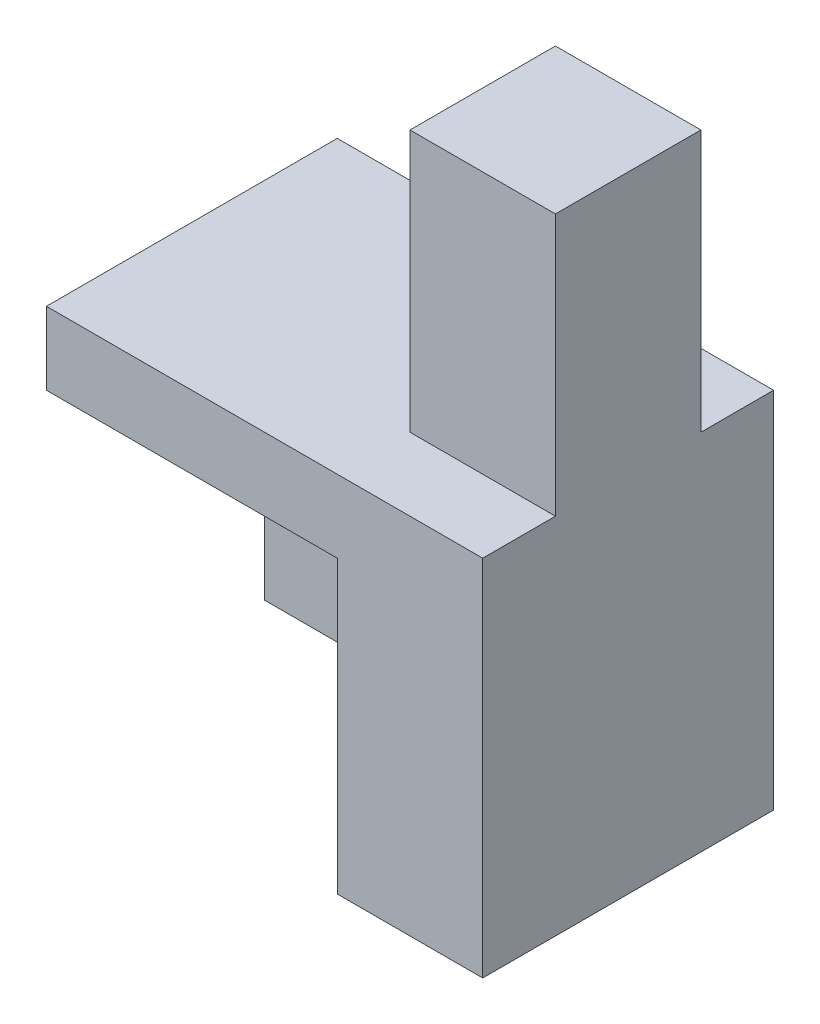
SolidWorks part; units mm, degrees
ref_plane "Front Plane" through (0, 0, 0) normal (0, 0, 1) x (1, 0, 0)
ref_plane "Top Plane" through (0, 0, 0) normal (0, 1, 0) x (1, 0, 0)
ref_plane "Right Plane" through (0, 0, 0) normal (1, 0, 0) x (0, 0, -1)
sketch "Sketch3" plane through (0, 0, 0) normal (0, 0, 1) x (1, 0, 0)
  line L0 (0, 0) -> (0, -5)
  line L1 (0, -5) -> (20, -5)
  line L2 (20, -5) -> (20, -25)
  line L3 (0, 0) -> (20, 0)
  line L4 (20, 0) -> (20, 18)
  line L5 (20, 18) -> (30, 18)
  line L6 (30, 18) -> (30, -25)
  line L7 (30, -25) -> (20, -25)
  dimension "D1" = 20
  dimension "D2" = 20
  dimension "D3" = 20
  dimension "D4" = 5
  dimension "D5" = 10
  dimension "D6" = 43
extrude "Boss-Extrude3" add sketch "Sketch3" along normal blind 10
sketch "Sketch4" plane through (0, 0, 0) normal (0, 0, -1) x (-1, 0, 0)
  line L5 (0, 0) -> (-30, 0)
  line L6 (0, 0) -> (0, -25)
  line L7 (0, -25) -> (-30, -25)
  line L8 (-30, 0) -> (-30, -25)
extrude "Boss-Extrude4" add sketch "Sketch4" along normal blind 5
sketch "Sketch5" plane through (0, 0, 10) normal (0, 0, 1) x (1, 0, 0)
  line L0 (0, 0) -> (0, -5)
  line L1 (0, -5) -> (20, -5)
  line L2 (20, -5) -> (20, -25)
  line L3 (20, -25) -> (30, -25)
  line L4 (30, -25) -> (30, 0)
  line L5 (30, 0) -> (0, 0)
extrude "Boss-Extrude5" add sketch "Sketch5" along normal blind 5
